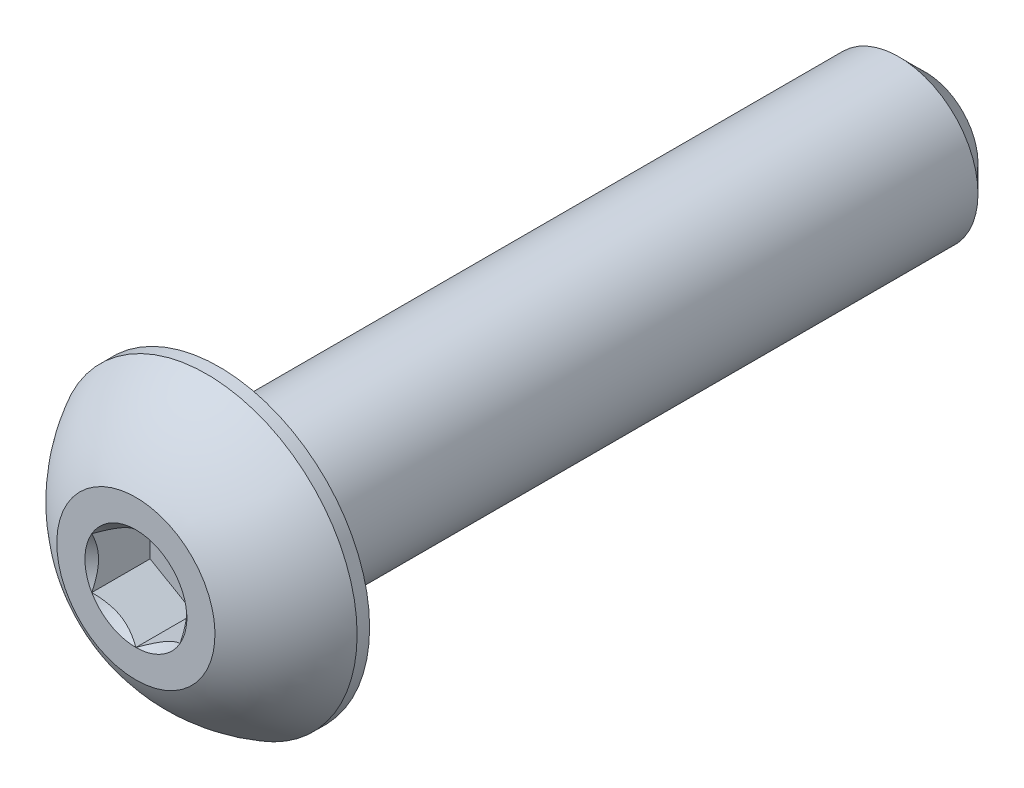
SolidWorks part; units mm, degrees
material "Alloy Steel"
ref_plane "Front" through (0, 0, 0) normal (0, 0, 1) x (1, 0, 0)
ref_plane "Top" through (0, 0, 0) normal (0, 1, 0) x (1, 0, 0)
ref_plane "Right" through (0, 0, 0) normal (1, 0, 0) x (0, 0, -1)
sketch "Sketch1" plane through (0, 0, 0) normal (1, 0, 0) x (0, 0, -1)
  line L2 (1.4986, 1.4224) -> (14.1986, 1.4224)
  line L3 (14.1986, 1.4224) -> (14.1986, 0)
  line L4 (14.1986, 0) -> (1.4986, 0)
  line L6 (1.2738, 2.7051) -> (1.4986, 2.7051) construction
  line L7 (14.1986, 1.4224) -> (14.1986, -1.4224) construction
  line L8 (0, 0) -> (1.4986, 0) construction
  line L9 (1.4986, 2.7051) -> (1.4986, -2.7051) construction
  line L11 (1.4986, 1.4224) -> (1.4986, 0)
  line L13 (0, 0.7937) -> (0, -0.7937) construction
  line L14 (0, 0.7937) -> (0, 1.4224) construction
  arc A3 (0, 1.4224) -> (1.2738, 2.7051) centre (2.7151, 0) cw construction
  dimension "D1" = 0.2248
revolve "Revolve1" add sketch "Sketch1" angle 360 mid plane about L4
sketch "Sketch3" plane through (0, 0, -14.1986) normal (0, 0, -1) x (-1, 0, 0)
  circle A0 centre (0, 0) radius 1.4224
curve "Helix/Spiral1" pitch 0.635 height 13.335 turns 21
sketch "Sketch2" plane through (0, 0, 0) normal (1, 0, 0) x (0, 0, -1)
  line L0 (14.1986, 1.4224) -> (14.7542, 1.4224)
  line L1 (14.7542, 1.4224) -> (14.5161, 1.01)
  line L2 (14.5161, 1.01) -> (14.4367, 1.01)
  line L3 (14.4367, 1.01) -> (14.1986, 1.4224)
  line L4 (14.3177, 1.2162) -> (14.6352, 1.2162) construction
  dimension "D1" = 60
  dimension "D2" = 0.0794
  dimension "D3" = 0.3175
chamfer "Chamfer1" distance 0.4763 angle 45 1 edges at (0, 1.4224, -14.1986)
sweep "Cut-Sweep1" [suppressed] cut profiles "Sketch2" path "Helix/Spiral1"
sketch "Sketch7" plane through (0, 0, 0) normal (1, 0, 0) x (0, 0, -1)
  line L6 (1.2738, 2.7051) -> (1.4986, 2.7051) construction
  line L8 (0, 0) -> (1.4986, 0) construction
  line L11 (1.4986, 2.7051) -> (1.4986, -2.7051) construction
  line L12 (1.2738, 2.7051) -> (1.4986, 2.7051)
  line L13 (0, 0) -> (1.4986, 0)
  line L14 (0, 0.7937) -> (0, -0.7937) construction
  line L15 (1.4986, 2.7051) -> (1.4986, 0)
  line L16 (0, 1.4224) -> (0, 0)
  arc A2 (1.2738, 2.7051) -> (0, 1.4224) centre (2.7151, 0) ccw construction
  arc A3 (1.2738, 2.7051) -> (0, 1.4224) centre (2.7151, 0) ccw
revolve "Revolve2" add sketch "Sketch7" angle 360 mid plane about L13
sketch "Sketch5" plane through (0, 0, 0) normal (0, 0, 1) x (1, 0, 0)
  line L1 (0.7937, -0.4583) -> (0.7937, 0.4583)
  line L2 (0.7937, 0.4583) -> (0, 0.9165)
  line L3 (0, 0.9165) -> (-0.7937, 0.4583)
  line L4 (-0.7937, 0.4583) -> (-0.7937, -0.4583)
  line L5 (-0.7937, -0.4583) -> (0, -0.9165)
  line L6 (0, -0.9165) -> (0.7937, -0.4583)
  circle A0 centre (0, 0) radius 0.7937 construction
extrude "Cut-Extrude2" cut sketch "Sketch5" against normal blind 1.049
sketch "Sketch6" plane through (0, 0, 0) normal (0, 0, 1) x (1, 0, 0)
  circle A0 centre (0, 0) radius 0.9165
extrude "Cut-Extrude3" cut sketch "Sketch6" against normal blind 1.049 draft 45
sketch "Sketch9" [suppressed] plane through (0, 0, -2.2098) normal (0, 0, 1) x (1, 0, 0)
  circle A2 centre (0, 0) radius 2.0828
extrude "Boss-Extrude2" [suppressed] add sketch "Sketch9" against normal offset from surface (3.175 mm away) 22.225
sketch "Sketch10" plane through (0, 0, 0) normal (1, 0, 0) x (0, 0, -1)
  line L0 (14.1986, 1.4224) -> (14.1986, -1.4224) construction
  point P0 (13.2461, -1.4224)
  dimension "D1" = 0.9525
equation "\"D3@Helix/Spiral1\" = \"Lg@Sketch1\" + \"D4@Helix/Spiral1\""
equation "\"D2@Sketch2\" = \"D4@Helix/Spiral1\" * .125"
equation "\"D3@Sketch2\" = \"D4@Helix/Spiral1\" * .5"
equation "\"D1@Chamfer1\" = \"D4@Helix/Spiral1\" * .75"
equation "\"D1@Cut-Extrude2\" = \"Head Ht@Sketch1\" * .7"
equation "\"D1@Sketch1\" = \"Head Ht@Sketch1\" * .15"
equation "\"D1@Sketch10\" = \"D4@Helix/Spiral1\" * 1.5"
equation "\"D1@Cut-Extrude3\" = \"D1@Cut-Extrude2\""
